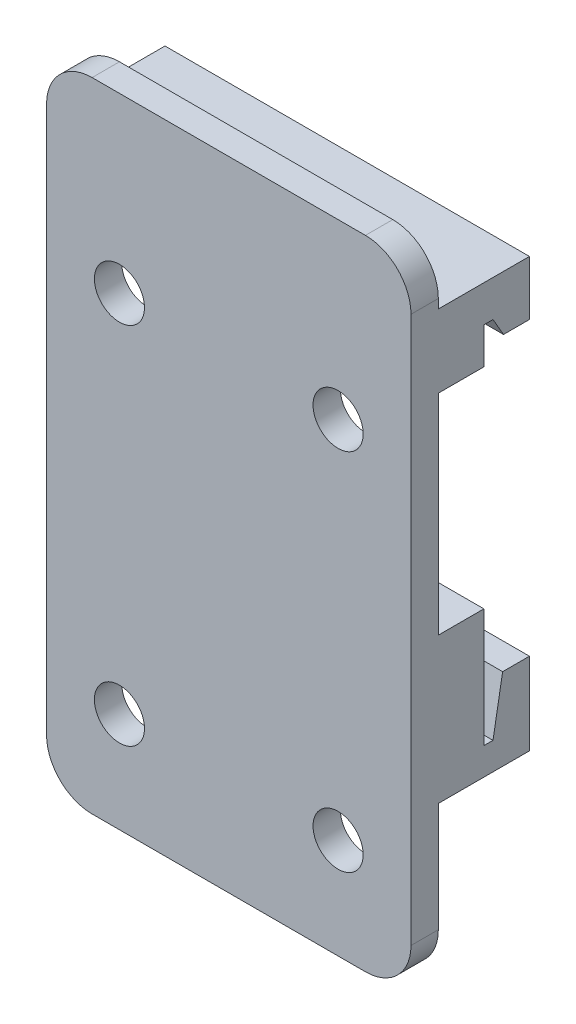
SolidWorks part; units mm, degrees
ref_plane "Front Plane" through (0, 0, 0) normal (0, 0, 1) x (1, 0, 0)
ref_plane "Top Plane" through (0, 0, 0) normal (0, 1, 0) x (1, 0, 0)
ref_plane "Right Plane" through (0, 0, 0) normal (1, 0, 0) x (0, 0, -1)
sketch "Sketch1" plane through (0, 0, 0) normal (0, 0, 1) x (1, 0, 0)
  line L1 (-20, 35) -> (20, 35)
  line L2 (-20, 35) -> (-20, -35)
  line L3 (-20, -35) -> (20, -35)
  line L4 (20, 35) -> (20, -35)
  line L5 (-20, 35) -> (20, -35) construction
  line L6 (-20, -35) -> (20, 35) construction
  point P0 (0, 0)
  dimension "D1" = 40
  dimension "D2" = 70
extrude "Boss-Extrude1" add sketch "Sketch1" along normal blind 3
sketch "Sketch2" plane through (0, 0, 0) normal (1, 0, 0) x (0, 0, -1)
  line L0 (0, 29) -> (10, 29)
  line L1 (0, 22.0001) -> (0, -22.0001) construction
  line L2 (10, 29) -> (10, 23)
  line L3 (10, 23) -> (7.1547, 23)
  line L4 (7.1547, 23) -> (6, 25)
  line L5 (6, 25) -> (5, 25)
  line L6 (0, 21) -> (0, 29)
  line L7 (7.15, 0) -> (-7.15, 0) construction
  line L8 (5, 25) -> (5, 21)
  line L9 (5, 21) -> (0, 21)
  dimension "D1" = 10
  dimension "D2" = 8
  dimension "D3" = 6
  dimension "D4" = 1
  dimension "D5" = 120
  dimension "D6" = 29
  dimension "D7" = 5
  dimension "D8" = 4
extrude "Boss-Extrude2" add sketch "Sketch2" along normal mid plane 40
sketch "Sketch3" plane through (0, 0, 0) normal (1, 0, 0) x (0, 0, -1)
  line L0 (0, -18) -> (10, -18)
  line L1 (0, 22.0001) -> (0, -22.0001) construction
  line L2 (10, -18) -> (10, -9)
  line L3 (10, -9) -> (7.058, -9)
  line L4 (7.058, -9) -> (6, -15)
  line L5 (6, -15) -> (5, -15)
  line L6 (0, -2) -> (0, -18)
  line L8 (7.15, 0) -> (-7.15, 0) construction
  line L9 (5, -15) -> (5, -2)
  line L10 (5, -2) -> (0, -2)
  dimension "D1" = 16
  dimension "D2" = 10
  dimension "D3" = 9
  dimension "D4" = 5
  dimension "D5" = 100
  dimension "D6" = 15
  dimension "D7" = 1
  dimension "D8" = 13
extrude "Boss-Extrude3" add sketch "Sketch3" along normal mid plane 40
extrude "Cut-Extrude1" cut sketch "Sketch3<2>" against normal mid plane 26
sketch "Sketch3<2>" plane through (0, 0, 0) normal (1, 0, 0) x (0, 0, -1) same geometry as "Sketch3"
sketch "Sketch4" plane through (0, 0, 0) normal (0, 0, 1) x (1, 0, 0)
  line L0 (13, -18) -> (-13, -18)
  line L1 (-13, -18) -> (-13, -15)
  line L2 (-13, -2) -> (-13, -18) construction
  line L3 (-13, -15) -> (11.2, -15)
  line L4 (13, -18) -> (13, -15)
  line L5 (13, -18) -> (13, -9) construction
  line L6 (0, -7.15) -> (0, 7.15) construction
  line L7 (-11, -11.5) -> (-11, -12.5)
  spline S0 degree 3 poles (11.2, -15) (7.9887, -12.3054) (4.1311, -9.9812) (-4.0592, -9.9747) (-6.4384, -13.7576) (-9.2104, -14.2998) (-11, -12.5) knots 0 0 0 0 0.361861 0.445151 0.78982 1 1 1 1
  spline S1 degree 3 poles (13, -15) (9.0918, -11.7207) (5.1602, -9.0127) (-4.5285, -8.9425) (-6.5815, -13.3251) (-9.8688, -13.175) (-11, -11.5) knots 0 0 0 0 0.360138 0.439165 0.751266 1 1 1 1
  dimension "D10" = 2.5
  dimension "D1" = 3
  dimension "D2" = 3
  dimension "D3" = 5
  dimension "D4" = 6
  dimension "D5" = 1.2
  dimension "D6" = 2.2
  dimension "D7" = 1
  dimension "D8" = 11
  dimension "D9" = 1.8
extrude "Boss-Extrude4" add sketch "Sketch4" against normal blind 10
fillet "Fillet1" radius 5 4 edges at (20, -35, 1.5) (-20, -35, 1.5) (-20, 35, 1.5) (20, 35, 1.5)
sketch "Sketch5" plane through (0, 0, 0) normal (0, 0, 1) x (1, 0, 0)
  line L0 (-25.1979, -4) -> (31.5892, -4) construction
  line L1 (7.15, 0) -> (-7.15, 0) construction
  line L2 (0, 23.8624) -> (0, -24.2165) construction
  line L3 (0, -7.15) -> (0, 7.15) construction
  circle A0 centre (-12, 16) radius 2.75
  circle A1 centre (12, 16) radius 2.75
  circle A2 centre (-12, -24) radius 2.75
  circle A3 centre (12, -24) radius 2.75
  dimension "D1" = 5.5
  dimension "D2" = 12
  dimension "D3" = 20
  dimension "D4" = 4
extrude "Cut-Extrude2" cut sketch "Sketch5" along normal up to next
extrude "Cut-Extrude4" cut sketch "Sketch4<2>" against normal blind 2
sketch "Sketch4<2>" plane through (0, 0, 0) normal (0, 0, 1) x (1, 0, 0) same geometry as "Sketch4"
